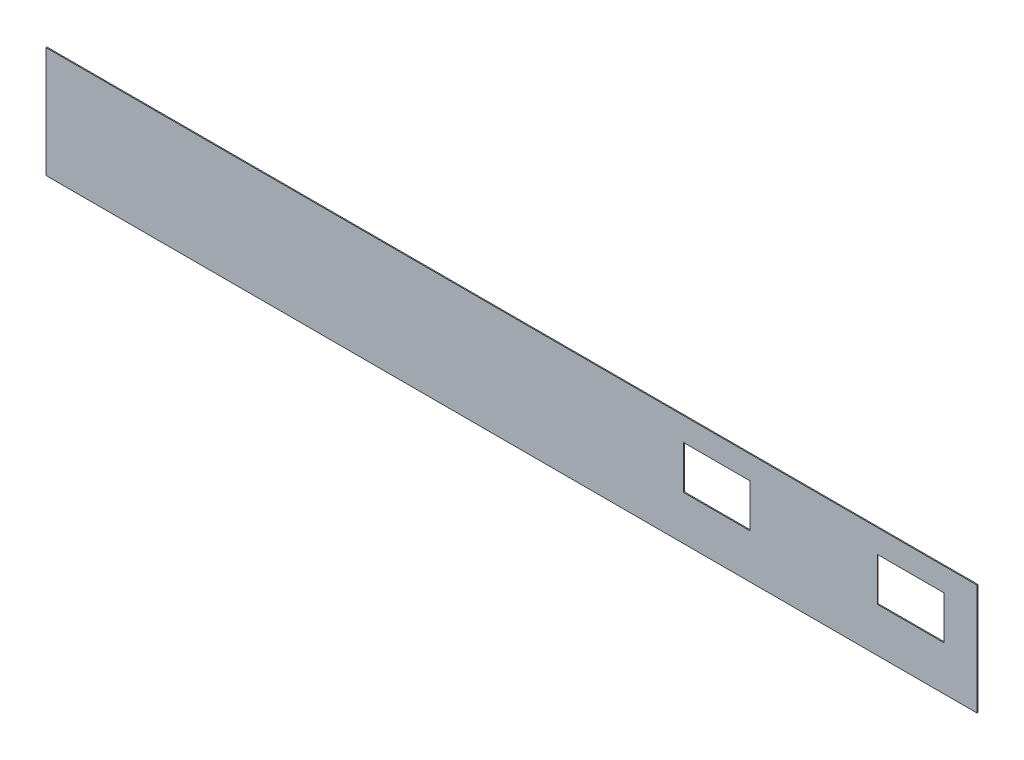
SolidWorks part; units mm, degrees
ref_plane "Front Plane" through (0, 0, 0) normal (0, 0, 1) x (1, 0, 0)
ref_plane "Top Plane" through (0, 0, 0) normal (0, 1, 0) x (1, 0, 0)
ref_plane "Right Plane" through (0, 0, 0) normal (1, 0, 0) x (0, 0, -1)
sketch "Sketch1" plane through (0, 0, 0) normal (0, 0, 1) x (1, 0, 0)
  line L0 (96, 0) -> (30, 0)
  line L1 (30, 0) -> (12, 0)
  line L2 (12, 0) -> (12, 10)
  line L3 (12, 10) -> (30, 10)
  line L4 (30, 10) -> (96, 10)
  line L5 (96, 10) -> (96, 0)
  line L6 (87, 4) -> (93, 4)
  line L7 (93, 4) -> (93, 7.9)
  line L8 (93, 7.9) -> (87, 7.9)
  line L9 (87, 7.9) -> (87, 4)
  line L10 (69.5, 4) -> (75.5, 4)
  line L11 (75.5, 4) -> (75.5, 7.9)
  line L12 (75.5, 7.9) -> (69.5, 7.9)
  line L13 (69.5, 7.9) -> (69.5, 4)
extrude "Boss-Extrude1" add sketch "Sketch1" along normal blind 0.09
